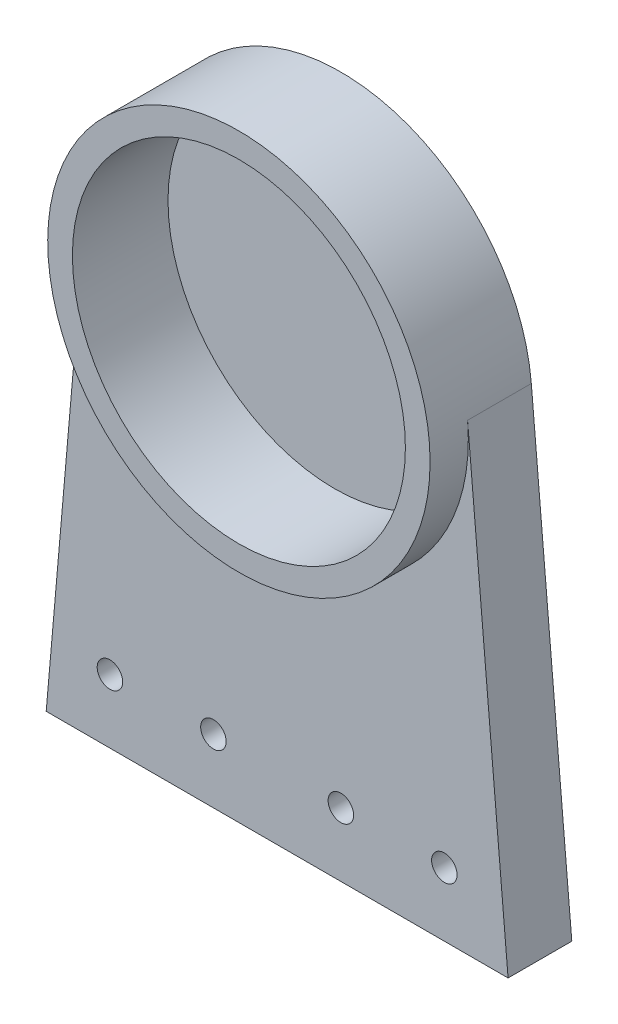
SolidWorks part; units mm, degrees
ref_plane "Front Plane" through (0, 0, 0) normal (0, 0, 1) x (1, 0, 0)
ref_plane "Top Plane" through (0, 0, 0) normal (0, 1, 0) x (1, 0, 0)
ref_plane "Right Plane" through (0, 0, 0) normal (1, 0, 0) x (0, 0, -1)
sketch "Sketch1" plane through (0, 0, 0) normal (0, 0, 1) x (1, 0, 0)
  circle A0 centre (0, 0) radius 26.125
  circle A1 centre (0, 0) radius 30
  dimension "D1" = 52.25
  dimension "D2" = 60
extrude "Boss-Extrude1" add sketch "Sketch1" along normal blind 15
sketch "Sketch2" plane through (0, 0, 0) normal (0, 0, -1) x (-1, 0, 0)
  circle A0 centre (0, 0) radius 30
extrude "Boss-Extrude2" add sketch "Sketch2" along normal blind 1
sketch "Sketch3" plane through (0, 0, -1) normal (0, 0, -1) x (-1, 0, 0)
  line L0 (0, 30) -> (0, -70) construction
  line L1 (-29.8858, 2.6147) -> (-36.2388, -70)
  line L2 (-36.2388, -70) -> (36.2388, -70)
  line L3 (29.8858, 2.6147) -> (36.2388, -70)
  circle A0 centre (0, 0) radius 30 construction
  arc A1 (-29.8858, 2.6147) -> (29.8858, 2.6147) centre (0, 0) ccw
  dimension "D1" = 85
  dimension "D2" = 70
extrude "Boss-Extrude3" add sketch "Sketch3" against normal blind 10
sketch "Sketch7" plane through (0, 0, 9) normal (0, 0, 1) x (1, 0, 0)
  line L0 (36.2388, -70) -> (-36.2388, -70) construction
  line L16 (0, 0) -> (0, -79.2627) construction
  circle A4 centre (10, -60) radius 2
  circle A5 centre (26.2388, -60) radius 2
  circle A6 centre (-26.2388, -60) radius 2
  circle A7 centre (-10, -60) radius 2
  dimension "D2" = 4
  dimension "D3" = 4
  dimension "D1" = 10
  dimension "D5" = 10
  dimension "D4" = 10
extrude "Cut-Extrude4" cut sketch "Sketch7" against normal blind 10
